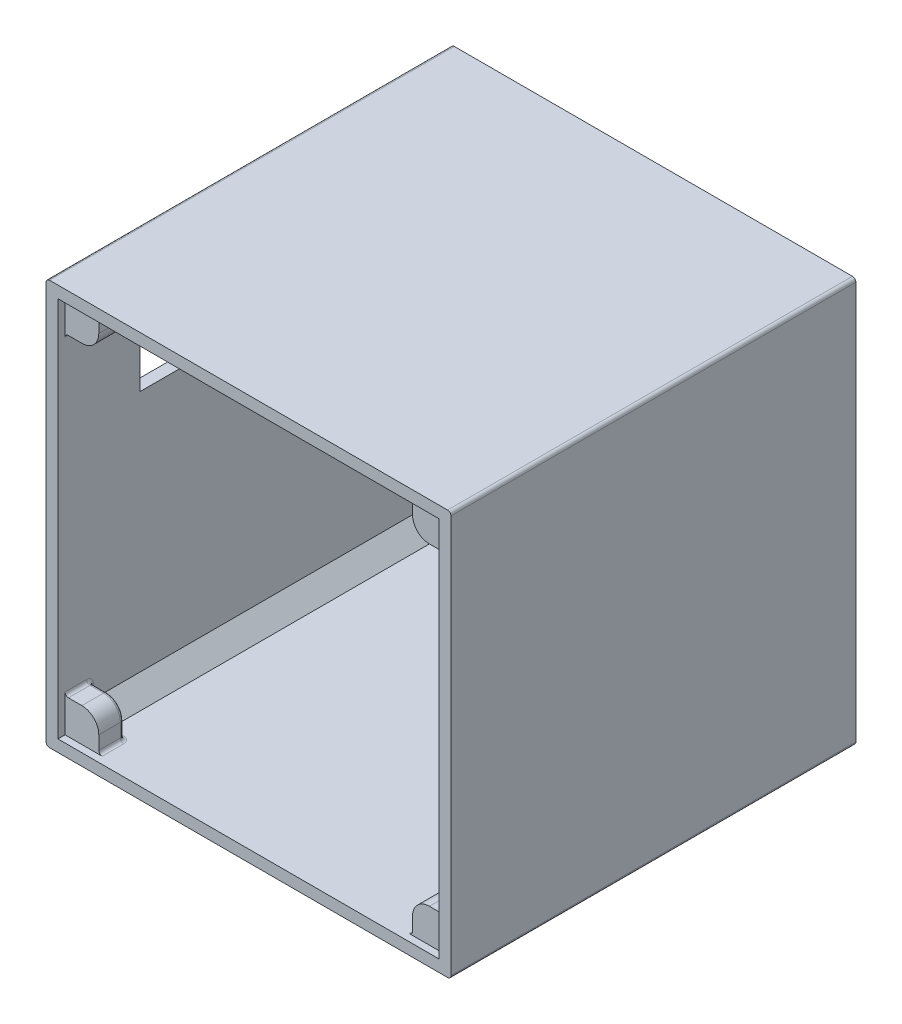
SolidWorks part; units mm, degrees
material "PVC 0.007 Plasticizado"
ref_plane "Plano frontal" through (0, 0, 0) normal (0, 0, 1) x (1, 0, 0)
ref_plane "Plano superior" through (0, 0, 0) normal (0, 1, 0) x (1, 0, 0)
ref_plane "Plano direito" through (0, 0, 0) normal (1, 0, 0) x (0, 0, -1)
sketch "Esboço2" plane through (0, 0, 0) normal (0, 0, 1) x (1, 0, 0)
  line L1 (-60, -60) -> (60, -60)
  line L2 (-60, -60) -> (-60, 60)
  line L3 (-60, 60) -> (60, 60)
  line L4 (60, -60) -> (60, 60)
  line L5 (-60, -60) -> (60, 60) construction
  line L6 (-60, 60) -> (60, -60) construction
  point P0 (0, 0)
extrude "Ressalto-extrusão1" add sketch "Esboço2" along normal blind 120
sketch "Esboço3" plane through (0, 0, 120) normal (0, 0, 1) x (1, 0, 0)
  line L8 (56.5, -56.5) -> (56.5, 56.5)
  line L9 (56.5, 56.5) -> (-56.5, 56.5)
  line L10 (-56.5, 56.5) -> (-56.5, -56.5)
  line L11 (-56.5, -56.5) -> (56.5, -56.5)
  line L12 (56.5, -56.5) -> (56.5, 56.5)
  line L13 (56.5, 56.5) -> (-56.5, 56.5)
  line L14 (-56.5, 56.5) -> (-56.5, -56.5)
  line L15 (-56.5, -56.5) -> (56.5, -56.5)
  dimension "D1" = 3.5
extrude "Corte-extrusão1" cut sketch "Esboço3" against normal blind 120
ref_plane "Plano1" through (0, 0, 0) normal (0, 0, 1) x (1, 0, 0)
ref_plane "Plano2" through (0, 0, 116.5) normal (0, 0, 1) x (1, 0, 0)
sketch "Esboço4" plane through (0, 0, 0) normal (0, 0, 1) x (1, 0, 0)
  line L0 (56.5, 56.5) -> (-56.5, 56.5) construction
  line L1 (-56.5, 56.5) -> (-56.5, -56.5) construction
  line L2 (-51.5, 46.5) -> (-56.5, 46.5)
  line L3 (-56.5, 46.5) -> (-56.5, 56.5)
  line L4 (-56.5, 56.5) -> (-46.5, 56.5)
  line L5 (-46.5, 56.5) -> (-46.5, 51.5)
  line L6 (0, -66) -> (0, 66) construction
  line L7 (46.5, 56.5) -> (46.5, 51.5)
  line L8 (56.5, 56.5) -> (46.5, 56.5)
  line L9 (56.5, 46.5) -> (56.5, 56.5)
  line L10 (51.5, 46.5) -> (56.5, 46.5)
  line L11 (66, 0) -> (-66, 0) construction
  line L12 (51.5, -46.5) -> (56.5, -46.5)
  line L13 (56.5, -46.5) -> (56.5, -56.5)
  line L14 (56.5, -56.5) -> (46.5, -56.5)
  line L15 (46.5, -56.5) -> (46.5, -51.5)
  line L16 (-46.5, -56.5) -> (-46.5, -51.5)
  line L17 (-56.5, -56.5) -> (-46.5, -56.5)
  line L18 (-56.5, -46.5) -> (-56.5, -56.5)
  line L19 (-51.5, -46.5) -> (-56.5, -46.5)
  line L20 (-51.5, 5) -> (-56.5, 5)
  line L21 (-56.5, 5) -> (-56.5, -5)
  line L22 (-56.5, -5) -> (-51.5, -5)
  line L23 (56.5, -5) -> (51.5, -5)
  line L24 (56.5, 5) -> (56.5, -5)
  line L25 (51.5, 5) -> (56.5, 5)
  line L26 (-5, 51.5) -> (-5, 56.5)
  line L27 (-5, 56.5) -> (5, 56.5)
  line L28 (5, 56.5) -> (5, 51.5)
  arc A0 (-51.5, 46.5) -> (-46.5, 51.5) centre (-51.5, 51.5) ccw
  arc A1 (51.5, 46.5) -> (46.5, 51.5) centre (51.5, 51.5) cw
  arc A2 (51.5, -46.5) -> (46.5, -51.5) centre (51.5, -51.5) ccw
  arc A3 (-51.5, -46.5) -> (-46.5, -51.5) centre (-51.5, -51.5) cw
  arc A4 (-51.5, -5) -> (-51.5, 5) centre (-51.5, 0) ccw
  arc A5 (51.5, -5) -> (51.5, 5) centre (51.5, 0) cw
  arc A6 (-5, 51.5) -> (5, 51.5) centre (0, 51.5) ccw
  dimension "D1" = 10
  dimension "D2" = 10
  dimension "D3" = 10
extrude "Ressalto-extrusão2" add sketch "Esboço4" along normal blind 7
sketch "Esboço5" plane through (0, 0, 116.5) normal (0, 0, 1) x (1, 0, 0)
  line L0 (-51.5, 46.5) -> (-56.5, 46.5)
  line L1 (-56.5, 46.5) -> (-56.5, 56.5)
  line L2 (-56.5, 56.5) -> (-46.5, 56.5)
  line L3 (-46.5, 56.5) -> (-46.5, 51.5)
  line L4 (46.5, 56.5) -> (46.5, 51.5)
  line L5 (56.5, 56.5) -> (46.5, 56.5)
  line L6 (56.5, 46.5) -> (56.5, 56.5)
  line L7 (51.5, 46.5) -> (56.5, 46.5)
  line L8 (51.5, -46.5) -> (56.5, -46.5)
  line L9 (56.5, -46.5) -> (56.5, -56.5)
  line L10 (56.5, -56.5) -> (46.5, -56.5)
  line L11 (46.5, -56.5) -> (46.5, -51.5)
  line L12 (-46.5, -56.5) -> (-46.5, -51.5)
  line L13 (-56.5, -56.5) -> (-46.5, -56.5)
  line L14 (-56.5, -46.5) -> (-56.5, -56.5)
  line L15 (-51.5, -46.5) -> (-56.5, -46.5)
  arc A0 (-51.5, 46.5) -> (-46.5, 51.5) centre (-51.5, 51.5) ccw
  arc A1 (51.5, 46.5) -> (46.5, 51.5) centre (51.5, 51.5) cw
  arc A2 (51.5, -46.5) -> (46.5, -51.5) centre (51.5, -51.5) ccw
  arc A3 (-51.5, -46.5) -> (-46.5, -51.5) centre (-51.5, -51.5) cw
  dimension "D1" = 10
ref_plane "Plano5" through (0, 0, 117.9) normal (0, 0, 1) x (1, 0, 0)
sketch "Esboço13" plane through (0, 0, 0) normal (0, 0, 1) x (1, 0, 0)
  line L0 (-56.5, -56.5) -> (56.5, -56.5) construction
  line L1 (-5, -51.5) -> (-5, -56.5)
  line L2 (-5, -56.5) -> (5, -56.5)
  line L3 (5, -56.5) -> (5, -51.5)
  arc A0 (5, -51.5) -> (-5, -51.5) centre (0, -51.5) ccw
  dimension "D1" = 10
extrude "Ressalto-extrusão6" add sketch "Esboço13" along normal blind 7
chamfer "Chanfro1" distance 5 angle 45 1 edges at (-56.5, 56.5, 63.5)
chamfer "Chanfro2" distance 5 angle 45 3 edges at (-56.5, -56.5, 63.5) (56.5, -56.5, 63.5) (56.5, 56.5, 63.5)
sketch "Esboço14" plane through (-60, 0, 0) normal (-1, 0, 0) x (0, 0, 1)
  line L0 (120, 60) -> (0, 60) construction
  line L1 (24.25, 45) -> (95.75, 45)
  line L2 (24.25, 45) -> (24.25, 20.5)
  line L3 (24.25, 20.5) -> (95.75, 20.5)
  line L4 (95.75, 45) -> (95.75, 20.5)
  line L5 (24.25, 45) -> (95.75, 20.5) construction
  line L6 (24.25, 20.5) -> (95.75, 45) construction
  point P0 (60, 32.75)
  point P5 (0, 0)
  point P8 (60, 60)
  dimension "D1" = 71.5
  dimension "D2" = 24.5
  dimension "D3" = 15
extrude "Corte-extrusão6" cut sketch "Esboço14" against normal blind 10
sketch "Esboço15" plane through (0, 0, 120) normal (0, 0, 1) x (1, 0, 0)
  line L1 (-56.5, -56.5) -> (56.5, -56.5)
  line L2 (-56.5, -56.5) -> (-56.5, 56.5)
  line L3 (-56.5, 56.5) -> (56.5, 56.5)
  line L4 (56.5, -56.5) -> (56.5, 56.5)
  line L5 (-56.5, -56.5) -> (56.5, 56.5) construction
  line L6 (-56.5, 56.5) -> (56.5, -56.5) construction
  point P0 (0, 0)
  point P5 (56.6625, -56.6625)
  dimension "D1" = 113
extrude "Corte-extrusão7" cut sketch "Esboço15" against normal blind 5
fillet "Filete3" radius 1 1 edges at (-60, 60, 60)
fillet "Filete4" radius 1 3 edges at (60, 60, 60) (60, -60, 60) (-60, -60, 60)
extrude "Ressalto-extrusão7" add sketch "Esboço5" against normal blind 6 and the other way blind 1.4
fillet "Filete8" radius 1 88 edges at (56.5, 46.5, 3.5) (46.5, 56.5, 3.5) (54, 46.5, 7) (47.9645, 47.9645, 7) (46.5, 54, 7) (49, 56.5, 7) (54, 54, 7) (56.5, 49, 7) (56.5, -46.5, 114.2) (46.5, -56.5, 114.2) (-46.5, -56.5, 114.2) (-56.5, -46.5, 114.2) (-56.5, 46.5, 114.2) (-46.5, 56.5, 114.2) (46.5, 56.5, 114.2) (56.5, 46.5, 114.2) (56.5, 5, 3.5) (56.5, -5, 3.5) (46.5, -56.5, 3.5) (56.5, -46.5, 3.5) (5, -56.5, 3.5) (-5, -56.5, 3.5) (-56.5, -46.5, 3.5) (-46.5, -56.5, 3.5) (-56.5, -5, 3.5) (-56.5, 5, 3.5) (-46.5, 56.5, 3.5) (-56.5, 46.5, 3.5) (-5, 56.5, 3.5) (5, 56.5, 3.5) (54, -46.5, 110.5) (47.9645, -47.9645, 110.5) (46.5, -54, 110.5) (49, -56.5, 110.5) (54, -54, 110.5) (56.5, -49, 110.5) (-49, -56.5, 110.5) (-46.5, -54, 110.5) (-47.9645, -47.9645, 110.5) (-54, -46.5, 110.5) (-56.5, -49, 110.5) (-54, -54, 110.5) (-54, 46.5, 110.5) (-47.9645, 47.9645, 110.5) (-46.5, 54, 110.5) (-49, 56.5, 110.5) (-54, 54, 110.5) (-56.5, 49, 110.5) (49, 56.5, 110.5) (46.5, 54, 110.5) (47.9645, 47.9645, 110.5) (54, 46.5, 110.5) (56.5, 49, 110.5) (54, 54, 110.5) (54, 5, 7) (56.5, 0, 7) (54, -5, 7) (46.5, 0, 7) (46.5, -54, 7) (47.9645, -47.9645, 7) (54, -46.5, 7) (56.5, -49, 7) (54, -54, 7) (49, -56.5, 7) (5, -54, 7) (0, -56.5, 7) (-5, -54, 7) (0, -46.5, 7) (-54, -46.5, 7) (-47.9645, -47.9645, 7) (-46.5, -54, 7) (-49, -56.5, 7) (-54, -54, 7) (-56.5, -49, 7) (-54, -5, 7) (-56.5, 0, 7) (-54, 5, 7) (-46.5, 0, 7) (-46.5, 54, 7) (-47.9645, 47.9645, 7) (-54, 46.5, 7) (-56.5, 49, 7) (-54, 54, 7) (-49, 56.5, 7) (0, 46.5, 7) (-5, 54, 7) (0, 56.5, 7) (5, 54, 7)
